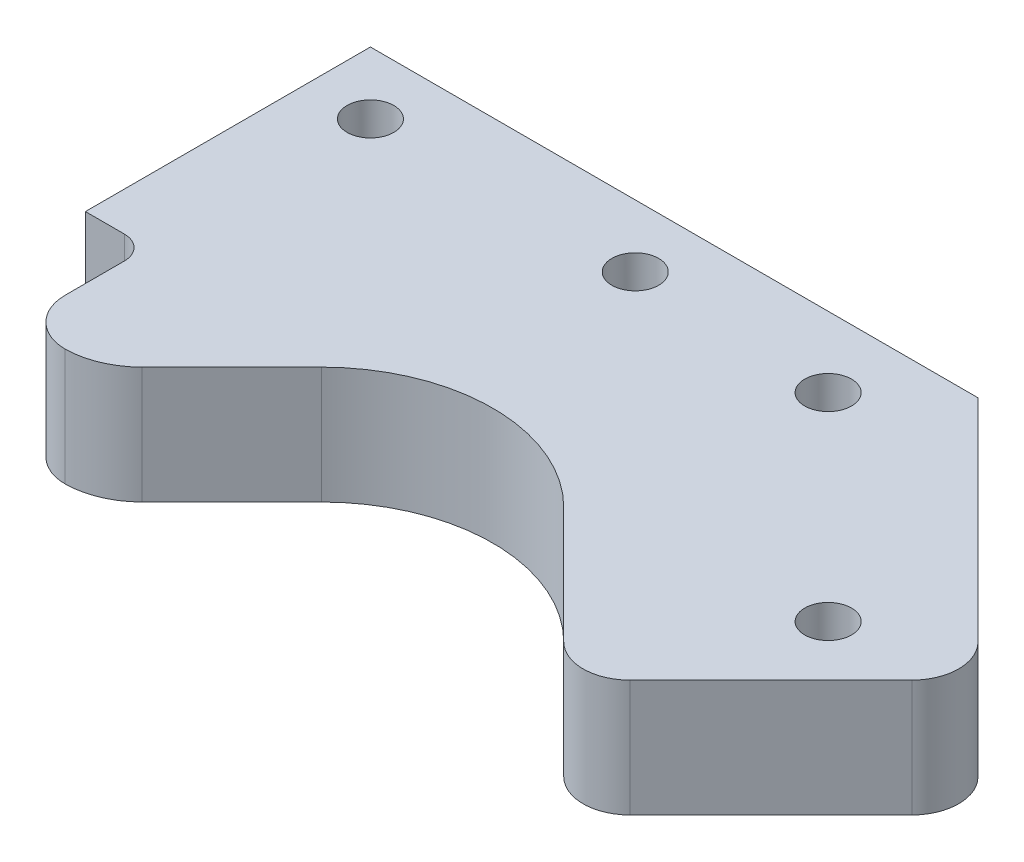
SolidWorks part; units mm, degrees
ref_plane "Front Plane" through (0, 0, 0) normal (0, 0, 1) x (1, 0, 0)
ref_plane "Top Plane" through (0, 0, 0) normal (0, 1, 0) x (1, 0, 0)
ref_plane "Right Plane" through (0, 0, 0) normal (1, 0, 0) x (0, 0, -1)
sketch "Sketch3" plane through (0, 5.4967, 0) normal (0, -1, 0) x (1, 0, 0)
  line L8 (-43.5722, -214.6789) -> (-43.5722, 19.4919) construction
  line L9 (-58.5723, 18.9356) -> (-63.5723, 18.9356)
  line L12 (-35.7941, 11.7137) -> (-26.1725, 21.3353)
  line L13 (-58.5723, 18.9356) -> (-51.3504, 11.7137)
  line L14 (-26.1725, 21.3353) -> (-12.8767, 8.0395)
  line L16 (-28.5722, -7.6561) -> (-12.8767, 8.0395)
  line L17 (-58.5723, -7.6561) -> (-28.5722, -7.6561)
  line L18 (-63.5723, 18.9356) -> (-63.5723, 5.6398)
  line L19 (-43.5722, 19.4919) -> (-32.5722, 19.4919) construction
  line L20 (-58.5723, -7.6561) -> (-63.5723, 5.6398)
  circle A0 centre (-43.5722, 19.4919) radius 11 construction
  arc A2 (-51.3504, 11.7137) -> (-35.7941, 11.7137) centre (-43.5722, 19.4919) ccw
  circle A4 centre (-33.6728, -3.1355) radius 1.5
  circle A5 centre (-20.9448, 9.5924) radius 1.5
extrude "Boss-Extrude1" add sketch "Sketch3" along normal blind 8
sketch "Sketch4" plane through (0, 25.4967, 0) normal (0, 1, 0) x (1, 0, 0)
  line L0 (-67.5734, 21.5545) -> (-67.5734, -11.9295) construction
  line L3 (-65.0723, -10.6398) -> (-67.5734, -10.6398)
  line L4 (-67.5734, 7.6561) -> (-67.5734, -10.6398)
  line L5 (-63.5723, -5.6398) -> (-63.5723, -18.9356)
  line L6 (-63.5723, -12.1398) -> (-63.5723, -18.9356)
  line L10 (-26.1725, -21.3353) -> (-12.8767, -8.0395)
  line L11 (-28.5722, 7.6561) -> (-58.5723, 7.6561)
  line L19 (-28.5722, 7.6561) -> (-67.5734, 7.6561)
  line L21 (-26.1725, -21.3353) -> (-12.8767, -8.0395)
  line L22 (-12.8767, -8.0395) -> (-28.5722, 7.6561)
  line L23 (-12.8767, -8.0395) -> (-28.5722, 7.6561)
  line L26 (-58.5723, 7.6561) -> (-63.5723, -5.6398)
  line L27 (-63.5723, -18.9356) -> (-58.5723, -18.9356)
  line L28 (-63.5723, -18.9356) -> (-58.5723, -18.9356)
  line L29 (-58.5723, -18.9356) -> (-51.3504, -11.7137)
  line L30 (-58.5723, -18.9356) -> (-51.3504, -11.7137)
  line L31 (-35.7941, -11.7137) -> (-26.1725, -21.3353)
  line L32 (-35.7941, -11.7137) -> (-26.1725, -21.3353)
  arc A1 (-35.7941, -11.7137) -> (-51.3504, -11.7137) centre (-43.5722, -19.4919) ccw
  arc A2 (-35.7941, -11.7137) -> (-51.3504, -11.7137) centre (-43.5722, -19.4919) ccw
  arc A3 (-63.5723, -12.1398) -> (-65.0723, -10.6398) centre (-65.0723, -12.1398) ccw
  dimension "D3" = 1.5
  dimension "D1" = 0
extrude "Boss-Extrude2" add sketch "Sketch4" along normal blind 8 separate body
sketch "Sketch9" plane through (0, 25.4967, 0) normal (0, -1, 0) x (1, 0, 0)
  line L0 (-34.7096, -7.6561) -> (-42.7096, 0.3439)
  line L2 (-42.7096, 0.3439) -> (-58.4567, 0.3439)
  line L3 (-34.7096, -7.6561) -> (-58.4567, -7.6561)
  line L4 (-58.4567, -7.6561) -> (-58.4567, 0.3439)
  line L6 (-58.5723, -7.6561) -> (-28.5722, -7.6561) construction
  line L7 (-20.9448, 9.5924) -> (-33.6728, -3.1355) construction
  dimension "D1" = 8
extrude "Boss-Extrude3" add sketch "Sketch9" along normal up to surface (20 mm away) up to face at (-44.3395, 5.4967, 8.6421)
sketch "Sketch10" plane through (0, 0, -7.6561) normal (0, 0, -1) x (-1, 0, 0)
  circle A0 centre (43.5723, 15.4967) radius 5
  circle A1 centre (43.5723, 15.4967) radius 7.5
extrude "Boss-Extrude4" add sketch "Sketch10" along normal blind 10
fillet "Fillet1" radius 3 6 edges at (-26.1725, 29.4967, 21.3353) (-12.8767, 29.4967, 8.0395) (-26.1725, 1.4967, 21.3353) (-12.8767, 1.4967, 8.0395) (-63.5723, 29.4967, 18.9356) (-63.5723, 1.4967, 18.9356)
sketch "Sketch11" plane through (0, 25.4967, 0) normal (0, -1, 0) x (1, 0, 0)
  line L12 (-58.5723, 18.9356) -> (-60.5723, 18.9356)
  line L13 (-63.5723, 15.9356) -> (-63.5723, 12.1398)
  line L15 (-67.5734, -7.6561) -> (-58.4567, -7.6561)
  line L16 (-58.4567, -7.6561) -> (-58.4567, 0.3439)
  line L17 (-58.4567, 0.3439) -> (-42.7096, 0.3439)
  line L18 (-42.7096, 0.3439) -> (-34.7096, -7.6561)
  line L19 (-34.7096, -7.6561) -> (-28.5722, -7.6561)
  line L20 (-28.5722, -7.6561) -> (-14.998, 5.9181)
  line L21 (-14.998, 10.1608) -> (-24.0512, 19.214)
  line L22 (-28.2939, 19.214) -> (-35.7941, 11.7137)
  line L23 (-51.3504, 11.7137) -> (-58.5723, 18.9356)
  line L24 (-58.5723, 18.9356) -> (-60.5723, 18.9356)
  line L25 (-63.5723, 15.9356) -> (-63.5723, 12.1398)
  line L27 (-67.5734, -7.6561) -> (-58.4567, -7.6561)
  line L28 (-58.4567, -7.6561) -> (-58.4567, 0.3439)
  line L29 (-58.4567, 0.3439) -> (-42.7096, 0.3439)
  line L30 (-42.7096, 0.3439) -> (-34.7096, -7.6561)
  line L31 (-34.7096, -7.6561) -> (-28.5722, -7.6561)
  line L32 (-28.5722, -7.6561) -> (-14.998, 5.9181)
  line L33 (-14.998, 10.1608) -> (-24.0512, 19.214)
  line L34 (-28.2939, 19.214) -> (-35.7941, 11.7137)
  line L35 (-51.3504, 11.7137) -> (-58.5723, 18.9356)
  line L39 (-65.0723, 10.6398) -> (-67.5734, 10.6398)
  line L40 (-65.0723, 10.6398) -> (-67.5734, 10.6398)
  line L41 (-67.5734, 10.6398) -> (-67.5734, -7.6561)
  line L42 (-67.5734, 10.6398) -> (-67.5734, -7.6561)
  arc A4 (-60.5723, 18.9356) -> (-63.5723, 15.9356) centre (-60.5723, 15.9356) ccw
  arc A5 (-14.998, 5.9181) -> (-14.998, 10.1608) centre (-17.1193, 8.0395) ccw
  arc A6 (-24.0512, 19.214) -> (-28.2939, 19.214) centre (-26.1725, 17.0926) ccw
  arc A7 (-51.3504, 11.7137) -> (-35.7941, 11.7137) centre (-43.5722, 19.4919) ccw
  arc A8 (-60.5723, 18.9356) -> (-63.5723, 15.9356) centre (-60.5723, 15.9356) ccw
  arc A9 (-14.998, 5.9181) -> (-14.998, 10.1608) centre (-17.1193, 8.0395) ccw
  arc A10 (-24.0512, 19.214) -> (-28.2939, 19.214) centre (-26.1725, 17.0926) ccw
  arc A11 (-51.3504, 11.7137) -> (-35.7941, 11.7137) centre (-43.5722, 19.4919) ccw
  arc A14 (-65.0723, 10.6398) -> (-63.5723, 12.1398) centre (-65.0723, 12.1398) ccw
  arc A15 (-65.0723, 10.6398) -> (-63.5723, 12.1398) centre (-65.0723, 12.1398) ccw
  dimension "D1" = 0
extrude "Cut-Extrude1" cut sketch "Sketch11" against normal blind 0.5
sketch "Sketch12" plane through (0, 5.4967, 0) normal (0, 1, 0) x (1, 0, 0)
  line L0 (-67.5734, -10.6398) -> (-65.0723, -10.6398) construction
  line L1 (-67.5734, 7.6561) -> (-67.5734, -10.6398) construction
  line L3 (-67.5734, -10.6398) -> (-65.0723, -10.6398)
  line L4 (-67.5734, 7.6561) -> (-67.5734, -10.6398)
  line L5 (-65.6492, -5.6398) -> (-67.5734, 7.6561)
  line L12 (-63.5723, -5.6398) -> (-63.5723, -15.9356)
  line L13 (-60.5723, -18.9356) -> (-58.5723, -18.9356)
  line L14 (-58.5723, -18.9356) -> (-51.3504, -11.7137)
  line L15 (-35.7941, -11.7137) -> (-28.2939, -19.214)
  line L16 (-24.0512, -19.214) -> (-14.998, -10.1608)
  line L17 (-14.998, -5.9181) -> (-28.5722, 7.6561)
  line L18 (-28.5722, 7.6561) -> (-34.7096, 7.6561)
  line L19 (-34.7096, 7.6561) -> (-42.7096, -0.3439)
  line L20 (-42.7096, -0.3439) -> (-58.4567, -0.3439)
  line L21 (-58.4567, -0.3439) -> (-58.4567, 7.6561)
  line L22 (-58.4567, 7.6561) -> (-58.5723, 7.6561)
  line L23 (-58.5723, 7.6561) -> (-63.5723, -5.6398)
  line L24 (-63.5723, -12.1398) -> (-63.5723, -15.9356)
  line L25 (-60.5723, -18.9356) -> (-58.5723, -18.9356)
  line L26 (-58.5723, -18.9356) -> (-51.3504, -11.7137)
  line L27 (-35.7941, -11.7137) -> (-28.2939, -19.214)
  line L28 (-24.0512, -19.214) -> (-14.998, -10.1608)
  line L29 (-14.998, -5.9181) -> (-28.5722, 7.6561)
  line L30 (-28.5722, 7.6561) -> (-34.7096, 7.6561)
  line L31 (-34.7096, 7.6561) -> (-42.7096, -0.3439)
  line L32 (-42.7096, -0.3439) -> (-58.4567, -0.3439)
  line L33 (-58.4567, -0.3439) -> (-58.4567, 7.6561)
  line L34 (-58.4567, 7.6561) -> (-58.5723, 7.6561)
  line L35 (-58.5723, 7.6561) -> (-62.8412, -3.6957)
  arc A0 (-65.6492, -5.6398) -> (-62.8412, -3.6957) centre (-65.6492, -2.6398) ccw
  arc A1 (-65.0723, -10.6398) -> (-63.5723, -12.1398) centre (-65.0723, -12.1398) cw
  arc A4 (-63.5723, -15.9356) -> (-60.5723, -18.9356) centre (-60.5723, -15.9356) ccw
  arc A5 (-35.7941, -11.7137) -> (-51.3504, -11.7137) centre (-43.5722, -19.4919) ccw
  arc A6 (-28.2939, -19.214) -> (-24.0512, -19.214) centre (-26.1725, -17.0926) ccw
  arc A7 (-14.998, -10.1608) -> (-14.998, -5.9181) centre (-17.1193, -8.0395) ccw
  arc A8 (-63.5723, -15.9356) -> (-60.5723, -18.9356) centre (-60.5723, -15.9356) ccw
  arc A9 (-35.7941, -11.7137) -> (-51.3504, -11.7137) centre (-43.5722, -19.4919) ccw
  arc A10 (-28.2939, -19.214) -> (-24.0512, -19.214) centre (-26.1725, -17.0926) ccw
  arc A11 (-14.998, -10.1608) -> (-14.998, -5.9181) centre (-17.1193, -8.0395) ccw
  dimension "D1" = 0
extrude "Cut-Extrude2" cut sketch "Sketch12" against normal blind 0.5
chamfer "Chamfer1" distance 3 angle 45 1 edges at (-36.0723, 15.4967, -7.6561)
sketch "Sketch13" plane through (0, 25.9967, 0) normal (0, -1, 0) x (1, 0, 0)
  line L0 (-58.4567, -7.6561) -> (-58.4567, 0.3439) construction
  line L2 (-58.4567, -7.6561) -> (-58.4567, 0.3439)
  line L3 (-67.5734, 0.3439) -> (-67.5734, -7.6561)
  line L4 (-58.4567, 0.3439) -> (-67.5734, 0.3439)
  line L5 (-67.5734, -7.6561) -> (-58.4567, -7.6561) construction
  line L6 (-67.5734, -7.6561) -> (-58.4567, -7.6561)
  line L7 (-67.5734, -21.5548) -> (-67.5734, 11.9292) construction
extrude "Boss-Extrude5" add sketch "Sketch13" along normal up to surface (21 mm away) up to face at (-22.4448, 4.9967, 9.5924)
fillet "Fillet2" radius 15 1 edges at (-63.5723, 1.2467, 5.6398)
fillet "Fillet3" radius 5 2 edges at (-58.5723, 29.7467, 18.9356) (-58.5723, 1.2467, 18.9356)
sketch "Sketch14" plane through (0, -2.5033, 0) normal (0, -1, 0) x (1, 0, 0)
  line L10 (-62.6123, 3.0871) -> (-58.5723, -7.6561) construction
  line L11 (-63.5723, 15.9356) -> (-63.5723, 8.367) construction
  line L12 (-62.6123, 3.0871) -> (-58.5723, -7.6561)
  line L13 (-63.5723, 12.1398) -> (-63.5723, 8.367)
  line L19 (-67.5734, -7.6561) -> (-28.5722, -7.6561)
  line L20 (-28.5722, -7.6561) -> (-12.8767, 8.0395)
  line L21 (-12.8767, 8.0395) -> (-26.1725, 21.3353)
  line L22 (-26.1725, 21.3353) -> (-35.7941, 11.7137)
  line L23 (-51.3504, 11.7137) -> (-58.5723, 18.9356)
  line L24 (-58.5723, 18.9356) -> (-63.5723, 18.9356)
  line L25 (-63.5723, 18.9356) -> (-63.5723, 12.1398)
  line L26 (-65.0723, 10.6398) -> (-67.5734, 10.6398)
  line L27 (-67.5734, 10.6398) -> (-67.5734, -7.6561)
  line L28 (-67.5734, -7.6561) -> (-58.5723, -7.6561)
  line L35 (-65.0723, 10.6398) -> (-67.5734, 10.6398)
  line L36 (-67.5734, 10.6398) -> (-67.5734, -7.6561)
  arc A6 (-63.5723, 8.367) -> (-62.6123, 3.0871) centre (-48.5723, 8.367) ccw construction
  arc A7 (-63.5723, 8.367) -> (-62.6123, 3.0871) centre (-48.5723, 8.367) ccw
  arc A8 (-51.3504, 11.7137) -> (-35.7941, 11.7137) centre (-43.5722, 19.4919) ccw
  arc A9 (-65.0723, 10.6398) -> (-63.5723, 12.1398) centre (-65.0723, 12.1398) ccw
  arc A11 (-65.0723, 10.6398) -> (-63.5723, 12.1398) centre (-65.0723, 12.1398) ccw
  dimension "D1" = 0
extrude "Boss-Extrude6" add sketch "Sketch14" against normal up to surface (7.5 mm away) up to face at (-22.4448, 4.9967, 9.5924)
sketch "Sketch15" plane through (0, -2.5033, 0) normal (0, -1, 0) x (1, 0, 0)
  line L0 (-67.5734, -7.6561) -> (-28.5722, -7.6561) construction
  line L1 (-67.5734, 2.3439) -> (-42.5734, 2.3439)
  line L2 (-67.5734, 2.3439) -> (-67.5734, -7.6561)
  line L3 (-67.5734, -7.6561) -> (-42.5734, -7.6561)
  line L4 (-42.5734, 2.3439) -> (-42.5734, -7.6561)
extrude "Cut-Extrude3" cut sketch "Sketch15" against normal blind 3
sketch "Sketch17" plane through (0, 33.4967, 0) normal (0, 1, 0) x (1, 0, 0)
  line L4 (-67.5734, 7.6561) -> (-67.5734, -2.3439)
  line L5 (-42.5734, 7.6561) -> (-67.5734, 7.6561)
  line L6 (-42.5734, -2.3439) -> (-42.5734, 7.6561)
  line L7 (-67.5734, -2.3439) -> (-42.5734, -2.3439)
  line L8 (-67.5734, 7.6561) -> (-67.5734, -2.3439)
  line L9 (-42.5734, 7.6561) -> (-67.5734, 7.6561)
  line L10 (-42.5734, -2.3439) -> (-42.5734, 7.6561)
  line L11 (-67.5734, -2.3439) -> (-42.5734, -2.3439)
  dimension "D1" = 0
extrude "Cut-Extrude4" cut sketch "Sketch17" against normal blind 3
fillet "Fillet4" radius 3 4 edges at (-42.5734, 31.9967, 2.3439) (-42.5734, 31.9967, -7.6561) (-42.5734, -1.0033, 2.3439) (-42.5734, -1.0033, -7.6561)
sketch "Sketch18" plane through (0, -2.5033, 0) normal (0, -1, 0) x (1, 0, 0)
  circle A0 centre (-46.5734, -3.6561) radius 1.5
  circle A1 centre (-63.5734, -3.6561) radius 1.5
extrude "Cut-Extrude5" cut sketch "Sketch18" against normal up to surface (36 mm away) up to face at (-45.1492, 33.4967, 8.1147)
sketch "Sketch19" plane through (0, 33.4967, 0) normal (0, 1, 0) x (1, 0, 0)
  line L1 (-9.0755, 20.5785) -> (-72.5969, 20.5785)
  line L2 (-9.0755, 20.5785) -> (-9.0755, -23.7161)
  line L3 (-9.0755, -23.7161) -> (-72.5969, -23.7161)
  line L4 (-72.5969, 20.5785) -> (-72.5969, -23.7161)
extrude "Cut-Extrude6" cut sketch "Sketch19" against normal up to surface (28.5 mm away) up to face at (-44.9881, 4.9967, 9.2111)
chamfer "Chamfer2" distance 1.5 angle 45 2 edges at (-32.1728, -2.5033, -3.1355) (-19.4448, -2.5033, 9.5924)
